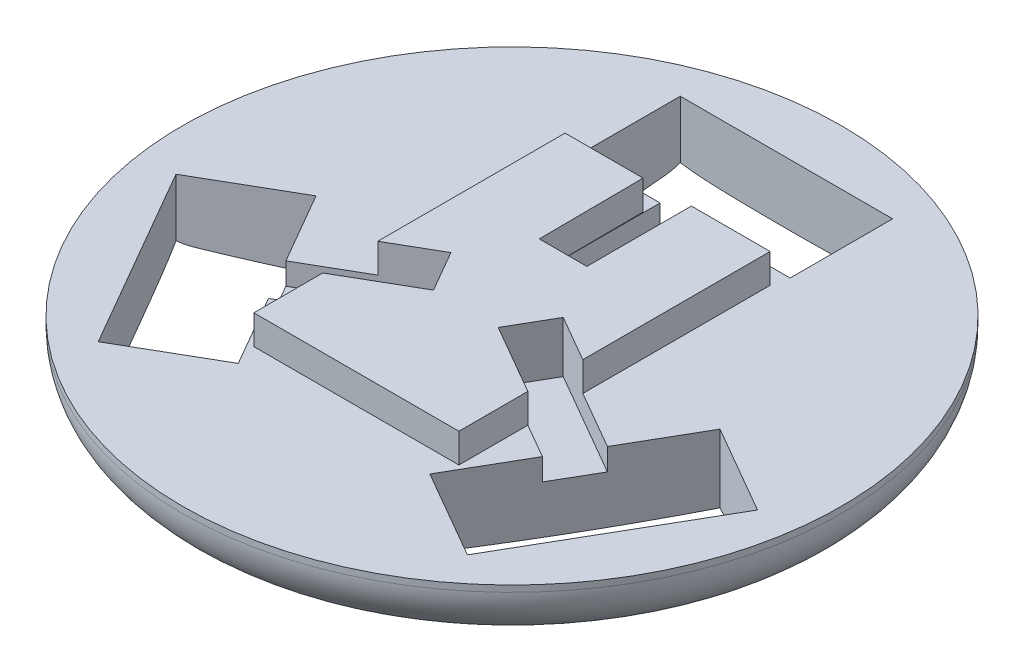
SolidWorks part; units mm, degrees
ref_plane "Front Plane" through (0, 0, 0) normal (0, 0, 1) x (1, 0, 0)
ref_plane "Top Plane" through (0, 0, 0) normal (0, 1, 0) x (1, 0, 0)
ref_plane "Right Plane" through (0, 0, 0) normal (1, 0, 0) x (0, 0, -1)
sketch "Sketch2" plane through (0, 0, 0) normal (0, 1, 0) x (1, 0, 0)
  line L0 (0, -68.0098) -> (0, 65.7503) construction
  line L1 (-29, 74.9495) -> (29, 74.9495)
  line L2 (-29, 74.9495) -> (-29, 46.9495)
  line L3 (-29, 46.9495) -> (29, 46.9495)
  line L4 (29, 74.9495) -> (29, 46.9495)
  line L5 (-29, 74.9495) -> (29, 46.9495) construction
  line L6 (-29, 46.9495) -> (29, 74.9495) construction
  line L7 (-70.2148, 0) -> (95.7201, 0) construction
  line L8 (0, 0) -> (-72.5813, -41.9048) construction
  line L9 (0, 0) -> (72.5813, -41.9048) construction
  line L10 (79.4081, -12.36) -> (50.4081, -62.5895)
  line L11 (55.1594, 1.64) -> (26.1594, -48.5895)
  line L12 (79.4081, -12.36) -> (55.1594, 1.64)
  line L13 (50.4081, -62.5895) -> (26.1594, -48.5895)
  line L14 (-50.4081, -62.5895) -> (-79.4081, -12.36)
  line L15 (-26.1594, -48.5895) -> (-55.1594, 1.64)
  line L16 (-50.4081, -62.5895) -> (-26.1594, -48.5895)
  line L17 (-79.4081, -12.36) -> (-55.1594, 1.64)
  line L18 (-6.5, -8.0505) -> (6.5, 46.9495) construction
  line L19 (-6.5, 46.9495) -> (6.5, 46.9495)
  line L20 (-6.5, 46.9495) -> (-6.5, -8.0505)
  line L21 (-6.5, -8.0505) -> (6.5, -8.0505)
  line L22 (6.5, 46.9495) -> (6.5, -8.0505)
  line L23 (-6.5, 46.9495) -> (6.5, -8.0505) construction
  line L24 (31.4023, -15.1408) -> (6.5, -0.7634)
  line L25 (-6.1216, -8.0505) -> (0, 2.5524)
  line L26 (24.9023, -26.3991) -> (0, -12.0218)
  line L27 (-25.0514, -26.4852) -> (0, -12.0218)
  line L28 (0, 2.5524) -> (6.1216, -8.0505)
  line L29 (-33.4324, -16.3129) -> (-6.5, -0.7634)
  circle A2 centre (0, 0) radius 16 construction
  point P3 (0, 19.4495)
  point P4 (0, 46.9495)
  point P6 (0, 60.9495)
  point P13 (0, 0)
  point P33 (0, 0)
  point P41 (0, -4.5162)
  dimension "D1" = 55
  dimension "D2" = 13
  dimension "D3" = 32
  dimension "D5" = 58
  dimension "D6" = 120
  dimension "D7" = 28
  dimension "D8" = 3
  dimension "D4" = 3
sketch "Sketch3" plane through (0, 0, 0) normal (1, 0, 0) x (0, 0, -1)
  line L0 (0, 83.7838) -> (0, -101.0811) construction
  line L1 (-115.9459, 0) -> (127.2973, 0) construction
  line L3 (90, 18.2691) -> (90, 20)
  line L5 (0, 20) -> (0, 0)
  line L6 (90, 20) -> (0, 20)
  arc A0 (0, 0) -> (76.6548, 3.3607) centre (13.1832, 575.2021) ccw
  arc A2 (90, 18.2691) -> (76.6548, 3.3607) centre (75, 18.2691) cw
  point P13 (90, 5)
  dimension "D5" = 15
  dimension "D1" = 15
  dimension "D2" = 20
  dimension "D3" = 20
  dimension "D4" = 90
revolve "Revolve1" add sketch "Sketch3" angle 360 about L5
extrude "Cut-Extrude1" cut sketch "Sketch2" along normal blind 40 contours L3 L4 L1 L2 | L15 L17 L14 L16 | L11 L13 L10 L12
sketch "Sketch4" plane through (0, 20, 0) normal (0, 1, 0) x (1, 0, 0)
  line L1 (-6.5, 46.9495) -> (6.5, 46.9495)
  line L2 (-6.5, 46.9495) -> (-6.5, 13.9495)
  line L3 (-6.5, 13.9495) -> (6.5, 13.9495)
  line L4 (6.5, 46.9495) -> (6.5, 13.9495)
  line L5 (-6.5, 46.9495) -> (6.5, 13.9495) construction
  line L6 (-6.5, 13.9495) -> (6.5, 46.9495) construction
  line L7 (43.9094, -17.8456) -> (37.4094, -29.1039)
  line L8 (-55.1594, 1.64) -> (-26.1594, -48.5895) construction
  line L9 (-29, 46.9495) -> (29, 46.9495) construction
  line L10 (55.1594, 1.64) -> (26.1594, -48.5895) construction
  line L26 (43.9094, -17.8456) -> (15.3306, -1.3456)
  line L27 (37.4094, -29.1039) -> (8.8306, -12.6039)
  line L28 (15.3306, -1.3456) -> (8.8306, -12.6039)
  line L29 (-37.4094, -29.1039) -> (-43.9094, -17.8456)
  line L30 (-37.4094, -29.1039) -> (-8.8306, -12.6039)
  line L31 (-43.9094, -17.8456) -> (-15.3306, -1.3456)
  line L32 (-8.8306, -12.6039) -> (-15.3306, -1.3456)
  point P0 (0, 30.4495)
  point P5 (0, 46.9495)
  point P22 (0, 0)
  point P23 (0, 4.0327)
  point P32 (-2.3282, 4.0326)
  line M8 (-55.1594, 1.64) -> (-26.1594, -48.5895)
  line M13 (26.1594, -48.5895) -> (55.1594, 1.64)
  line M17 (29, 46.9495) -> (-29, 46.9495)
  dimension "D1" = 13
  dimension "D2" = 33
extrude "Cut-Extrude2" cut sketch "Sketch4" against normal blind 6 contours L4 L2 L3 M17 | L30 L32 L31 M8 | L26 L28 L27 M13 region at (0, 20, -30.4495) region at (26.37, 20, 15.2247) region at (-26.37, 20, 15.2247)
sketch "Sketch5" plane through (0, 20, 0) normal (0, 1, 0) x (1, 0, 0)
  line L0 (-28, -23.6714) -> (-8.8306, -12.6039)
  line L1 (-28, 42.5) -> (-6.7113, 42.5)
  line L2 (-28, 42.5) -> (-28, -8.6603)
  line L3 (-28, -42.5) -> (28, -42.5)
  line L4 (28, 42.5) -> (28, -8.6603)
  line L5 (-28, 42.5) -> (28, -42.5) construction
  line L6 (-28, -42.5) -> (28, 42.5) construction
  line L7 (-37.4094, -29.1039) -> (-8.8306, -12.6039) construction
  line L8 (-8.8306, -12.6039) -> (-15.3306, -1.3456)
  line L9 (-15.3306, -1.3456) -> (-28, -8.6603)
  line L10 (-43.9094, -17.8456) -> (-15.3306, -1.3456) construction
  line L11 (28, -23.6714) -> (8.8306, -12.6039)
  line L12 (37.4094, -29.1039) -> (8.8306, -12.6039) construction
  line L13 (8.8306, -12.6039) -> (15.3306, -1.3456)
  line L14 (15.3306, -1.3456) -> (28, -8.6603)
  line L15 (-6.7113, 42.5) -> (-6.5, 13.9495)
  line L16 (-6.5, 13.9495) -> (6.5, 13.9495)
  line L17 (6.5, 13.9495) -> (6.5, 42.5)
  line L18 (6.5, 46.9495) -> (6.5, 13.9495) construction
  line L19 (6.5, 46.9495) -> (6.5, 13.9495) construction
  line L20 (-28, -23.6714) -> (-28, -42.5)
  line L21 (28, -23.6714) -> (28, -42.5)
  line L22 (6.5, 42.5) -> (28, 42.5)
  point P0 (0, 0)
  dimension "D1" = 56
  dimension "D2" = 85
extrude "Boss-Extrude1" add sketch "Sketch5" along normal blind 8
